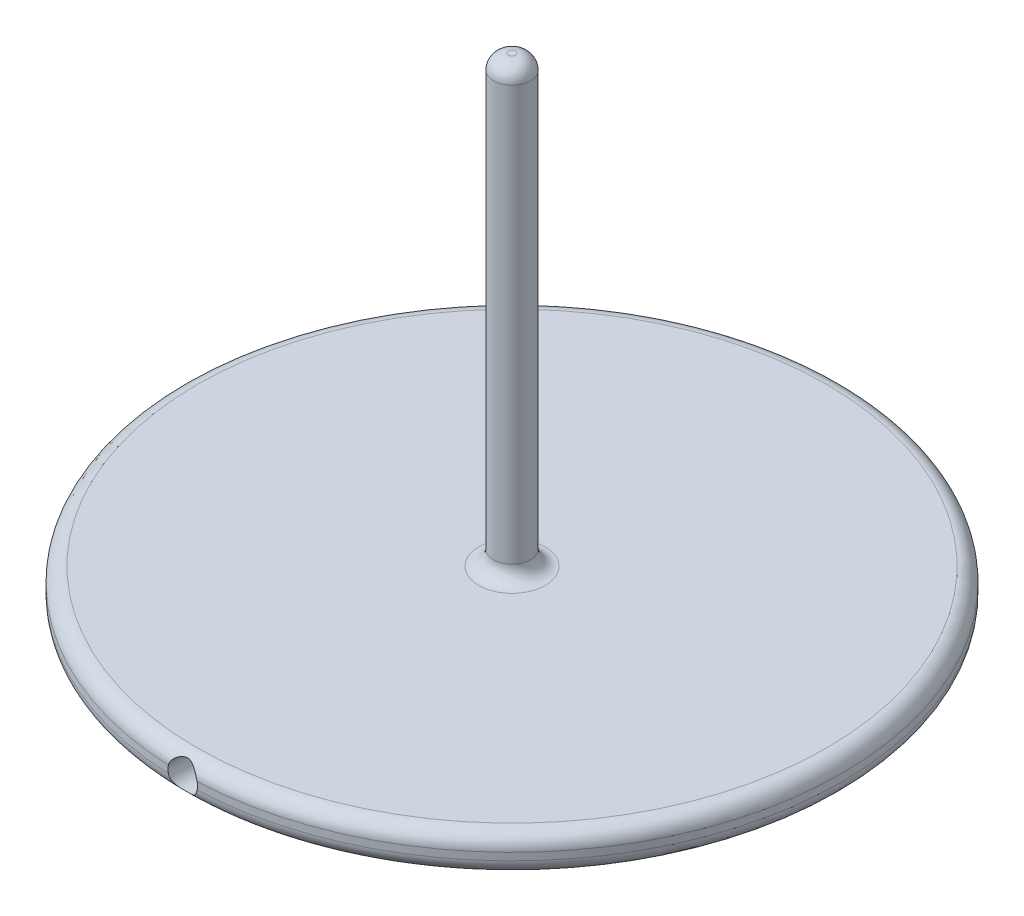
SolidWorks part; units mm, degrees
ref_plane "Front Plane" through (0, 0, 0) normal (0, 0, 1) x (1, 0, 0)
ref_plane "Top Plane" through (0, 0, 0) normal (0, 1, 0) x (1, 0, 0)
ref_plane "Right Plane" through (0, 0, 0) normal (1, 0, 0) x (0, 0, -1)
sketch "Sketch1" plane through (0, 0, 0) normal (0, 1, 0) x (1, 0, 0)
  circle A0 centre (0, 0) radius 56.515
  dimension "D1" = 113.03
extrude "Boss-Extrude1" add sketch "Sketch1" along normal blind 6.35
sketch "Sketch2" plane through (0, 6.35, 0) normal (0, 1, 0) x (1, 0, 0)
  circle A0 centre (0, 0) radius 3.175
  dimension "D1" = 6.35
extrude "Boss-Extrude2" add sketch "Sketch2" along normal blind 76.2
ref_plane "Plane1" through (0, 0, 56.515) normal (0, 0, 1) x (1, 0, 0)
sketch "Sketch5" plane through (0, 0, 56.515) normal (0, 0, 1) x (1, 0, 0)
  line L0 (0, 0) -> (0, 6.35)
  line L1 (56.515, 6.35) -> (-56.515, 6.35) construction
  circle A0 centre (0, 3.175) radius 2.54
  dimension "D1" = 5.08
extrude "Cut-Extrude1" cut sketch "Sketch5" against normal blind 25.4 contours A0
fillet "Fillet2" radius 2.54 4 edges at (0, 82.55, 3.175) (0, 6.35, 3.175) (0, 0, 56.515) (0, 6.35, 56.515)
